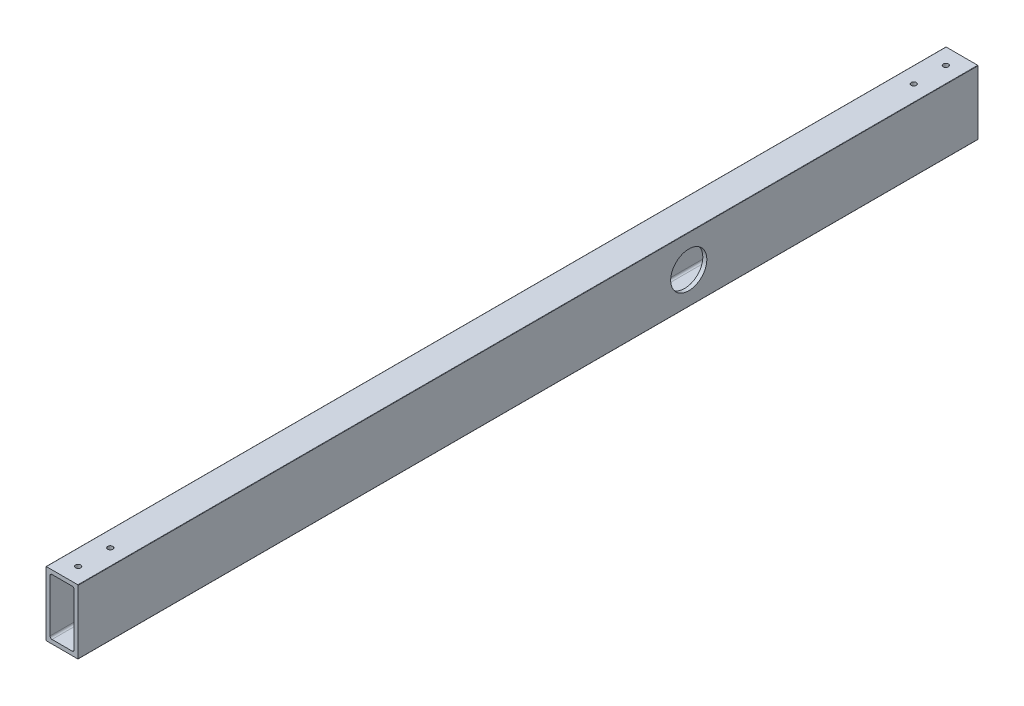
SolidWorks part; units mm, degrees
material "3.0205 (EN-AW 1200)"
ref_plane "Front Plane" through (0, 0, 0) normal (0, 0, 1) x (1, 0, 0)
ref_plane "Top Plane" through (0, 0, 0) normal (0, 1, 0) x (1, 0, 0)
ref_plane "Right Plane" through (0, 0, 0) normal (1, 0, 0) x (0, 0, -1)
ref_plane "Plane1" through (0, 0, 0) normal (0, 0, -1) x (-1, 0, 0)
sketch "Sketch1" plane through (0, 0, 0) normal (0, 0, -1) x (-1, 0, 0)
  line L0 (-3.175, 46.0375) -> (-3.175, 4.7625)
  line L1 (-4.7625, 3.175) -> (-20.6375, 3.175)
  line L2 (-22.225, 4.7625) -> (-22.225, 46.0375)
  line L3 (-20.6375, 47.625) -> (-4.7625, 47.625)
  line L4 (0, 0.254) -> (0, 50.546)
  line L5 (-0.254, 50.8) -> (-25.146, 50.8)
  line L6 (-25.4, 50.546) -> (-25.4, 0.254)
  line L7 (-25.146, 0) -> (-0.254, 0)
  arc A0 (-3.175, 4.7625) -> (-4.7625, 3.175) centre (-4.7625, 4.7625) cw
  arc A1 (-20.6375, 3.175) -> (-22.225, 4.7625) centre (-20.6375, 4.7625) cw
  arc A2 (-22.225, 46.0375) -> (-20.6375, 47.625) centre (-20.6375, 46.0375) cw
  arc A3 (-4.7625, 47.625) -> (-3.175, 46.0375) centre (-4.7625, 46.0375) cw
  arc A4 (-0.254, 0) -> (0, 0.254) centre (-0.254, 0.254) ccw
  arc A5 (0, 50.546) -> (-0.254, 50.8) centre (-0.254, 50.546) ccw
  arc A6 (-25.146, 50.8) -> (-25.4, 50.546) centre (-25.146, 50.546) ccw
  arc A7 (-25.4, 0.254) -> (-25.146, 0) centre (-25.146, 0.254) ccw
extrude "Boss-Extrude1" add sketch "Sketch1" against normal blind 711.2
sketch "Sketch2" plane through (0, 50.8, 0) normal (0, 1, 0) x (1, 0, 0)
  line L0 (0.254, -711.2) -> (25.146, -711.2) construction
  line L1 (25.146, -355.6) -> (0, -355.6) construction
  line L2 (25.146, -711.2) -> (25.146, 0) construction
  line L3 (0, -711.2) -> (0, 0) construction
  circle A0 centre (12.7, -698.5) radius 2.032
  circle A1 centre (12.7, -673.1) radius 2.032
  circle A2 centre (12.7, -38.1) radius 2.032
  circle A3 centre (12.7, -12.7) radius 2.032
  dimension "D1" = 4.064
  dimension "D2" = 4.064
  dimension "D3" = 12.7
  dimension "D4" = 25.4
extrude "Cut-Extrude1" cut sketch "Sketch2" against normal through all
ref_plane "Plane2" through (224.155, 46.0375, 596.9) normal (0, 0, -1) x (-1, 0, 0)
sketch "Sketch5" plane through (25.4, 0, 0) normal (1, 0, 0) x (0, 0, -1)
  line L0 (-711.2, 50.546) -> (0, 50.546) construction
  line L2 (0, 50.546) -> (0, 0.254) construction
  circle A0 centre (-228.6, 25.146) radius 14.2875
  dimension "D1" = 28.575
  dimension "D2" = 25.4
  dimension "D3" = 228.6
extrude "Cut-Extrude2" cut sketch "Sketch5" against normal through all
